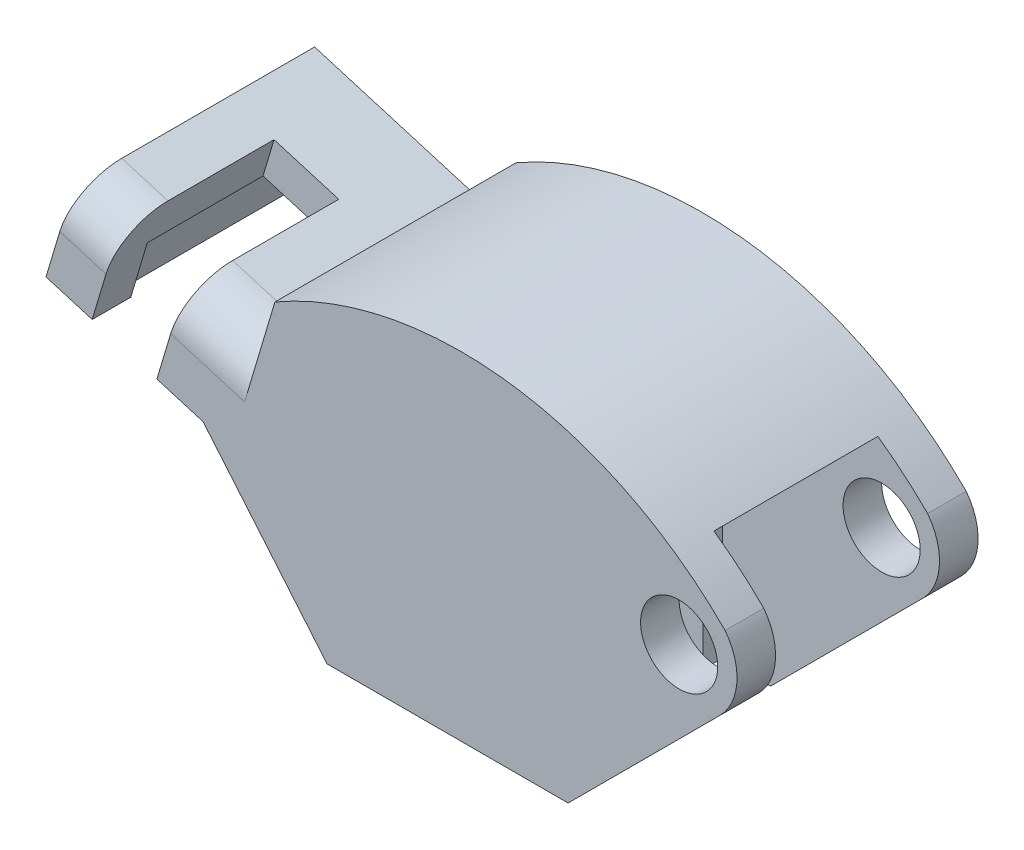
SolidWorks part; units mm, degrees
ref_plane "Front Plane" through (0, 0, 0) normal (0, 0, 1) x (1, 0, 0)
ref_plane "Top Plane" through (0, 0, 0) normal (0, 1, 0) x (1, 0, 0)
ref_plane "Right Plane" through (0, 0, 0) normal (1, 0, 0) x (0, 0, -1)
sketch "Sketch2" plane through (0, 0, 0) normal (0, 0, 1) x (1, 0, 0)
  line L0 (-10.8927, 0) -> (14.1073, 0)
  line L1 (14.1073, 0) -> (29.8646, 15.7574)
  line L2 (-10.8927, 0) -> (-23.7485, 15.3209)
  line L3 (51.2153, 35) -> (-56.25, 35)
  line L4 (-40.0398, 20.178) -> (-37.1827, 29.7612)
  line L5 (-23.7485, 15.3209) -> (-40.0398, 20.178)
  line L6 (-18.0164, 24.0469) -> (-16.3021, 29.7968)
  line L7 (14.1073, 0) -> (31.7849, 17.6777) construction
  line L8 (-18.0164, 24.0469) -> (-37.1827, 29.7612)
  line L9 (-6.2297, 10) -> (-18.0164, 24.0469) construction
  line L10 (-6.2297, 10) -> (9.9651, 10) construction
  line L11 (9.9651, 10) -> (24.7139, 24.7487) construction
  circle A0 centre (25.622, 20) radius 4
  arc A2 (29.8646, 15.7574) -> (30.3883, 23.6445) centre (25.622, 20) ccw
  arc A3 (-16.3021, 29.7968) -> (30.3883, 23.6445) centre (3.0495, -3.5874) cw
  dimension "D11" = 8
  dimension "D13" = 6
  dimension "D1" = 25
  dimension "D2" = 50
  dimension "D3" = 45
  dimension "D4" = 35
  dimension "D5" = 20
  dimension "D7" = 10
  dimension "D8" = 17
  dimension "D9" = 20
  dimension "D10" = 6
  dimension "D12" = 20
extrude "Boss-Extrude1" add sketch "Sketch2" along normal blind 25 contours A3 L6 L8 L4 L5 L2 L0 L1 A2 A0 region at (-0.9621, 17.9482, 0)
shell "Shell1" thickness 4 removed face at (1.6073, 0, 12.5) removed face at (21.9859, 7.8787, 12.5) removed face at (-17.3206, 7.6604, 12.5) removed face at (-31.8942, 17.7495, 12.5)
sketch "Sketch4" plane through (0, 0, 4) normal (0, 0, 1) x (1, 0, 0)
  line L0 (-3.8927, 0) -> (-3.8927, 16)
  line L1 (-10.8927, 0) -> (14.1073, 0) construction
  line L2 (-3.8927, 0) -> (6.1073, 0)
  line L3 (-3.8927, 16) -> (6.1073, 16)
  line L4 (6.1073, 16) -> (6.1073, 0)
  dimension "D2" = 10
  dimension "D3" = 16
extrude "Cut-Extrude1" cut sketch "Sketch4" against normal blind 2
sketch "Sketch5" plane through (0, 0, 21) normal (0, 0, -1) x (-1, 0, 0)
  line L0 (-6.1073, 0) -> (-6.1073, 16)
  line L1 (10.8927, 0) -> (-14.1073, 0) construction
  line L2 (3.8927, 0) -> (-6.1073, 0)
  line L3 (-6.1073, 16) -> (3.8927, 16)
  line L4 (3.8927, 16) -> (3.8927, 0)
  dimension "D1" = 16
  dimension "D2" = 10
extrude "Cut-Extrude2" cut sketch "Sketch5" against normal blind 2
sketch "Sketch12" plane through (0, 0, 0) normal (0, -1, 0) x (1, 0, 0)
  line L1 (-3.8927, 21) -> (-6.8927, 21)
  line L2 (-3.8927, 21) -> (-3.8927, 19)
  line L3 (-3.8927, 19) -> (-6.8927, 19)
  line L4 (-6.8927, 21) -> (-6.8927, 19)
  line L5 (6.1073, 21) -> (9.1073, 21)
  line L6 (6.1073, 21) -> (6.1073, 19)
  line L7 (6.1073, 19) -> (9.1073, 19)
  line L8 (9.1073, 21) -> (9.1073, 19)
  line L9 (-3.8927, 4) -> (-6.8927, 4)
  line L10 (-3.8927, 4) -> (-3.8927, 6)
  line L11 (-3.8927, 6) -> (-6.8927, 6)
  line L12 (-6.8927, 4) -> (-6.8927, 6)
  line L13 (6.1073, 4) -> (9.1073, 4)
  line L14 (6.1073, 4) -> (6.1073, 6)
  line L15 (6.1073, 6) -> (9.1073, 6)
  line L16 (9.1073, 4) -> (9.1073, 6)
  point P20 (-5.3927, 6)
  dimension "D1" = 3
  dimension "D2" = 3
  dimension "D3" = 3
  dimension "D4" = 3
  dimension "D5" = 2
  dimension "D6" = 2
  dimension "D7" = 2
  dimension "D8" = 2
extrude "Boss-Extrude2" add sketch "Sketch12" against normal up to surface (30.2961 mm away) up to face at (3.8834, 28.8205, 12.5)
sketch "Sketch13" plane through (0, 0, 25) normal (0, 0, 1) x (1, 0, 0)
  line L0 (-32.3911, 28.3326) -> (-35.2483, 18.7495)
  line L1 (-18.0164, 24.0469) -> (-37.1827, 29.7612) construction
  line L2 (-32.3911, 28.3326) -> (-25.6829, 26.3326)
  line L3 (-23.7485, 15.3209) -> (-40.0398, 20.178) construction
  line L4 (-25.6829, 26.3326) -> (-28.5401, 16.7495)
  line L5 (-28.5401, 16.7495) -> (-35.2483, 18.7495)
  dimension "D2" = 7
extrude "Cut-Extrude3" cut sketch "Sketch13" against normal blind 16
fillet "Fillet1" radius 5 2 edges at (-21.8497, 25.1898, 25) (-34.7869, 29.0469, 25)
sketch "Sketch14" plane through (0, 0, 4) normal (0, 0, 1) x (1, 0, 0)
  circle A0 centre (25.622, 20) radius 8
  dimension "D1" = 16
extrude "Cut-Extrude4" cut sketch "Sketch14" along normal up to surface (17 mm away) up to face at (14.8072, 13.4387, 21)
